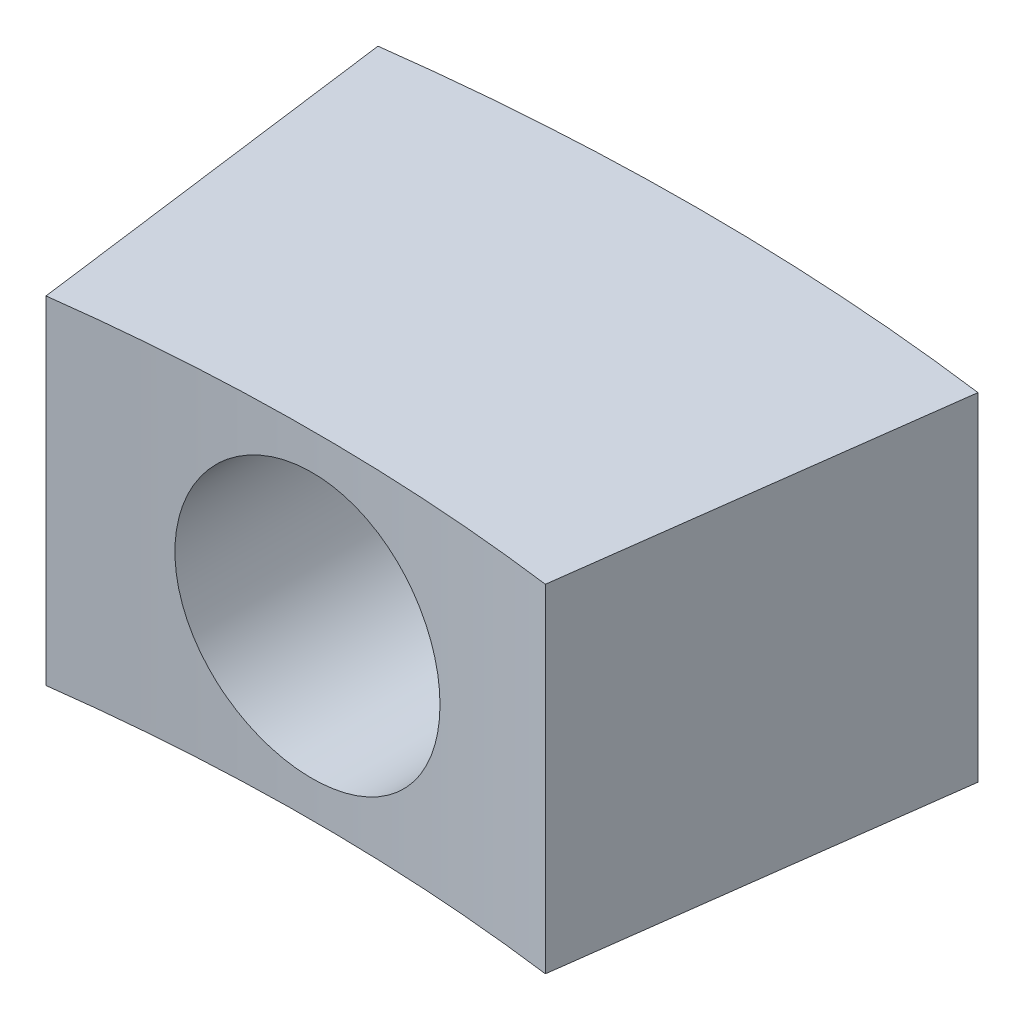
SolidWorks part; units mm, degrees
ref_plane "Front Plane" through (0, 0, 0) normal (0, 0, 1) x (1, 0, 0)
ref_plane "Top Plane" through (0, 0, 0) normal (0, 1, 0) x (1, 0, 0)
ref_plane "Right Plane" through (0, 0, 0) normal (1, 0, 0) x (0, 0, -1)
sketch "Sketch2" plane through (0, 0, 0) normal (0, 1, 0) x (1, 0, 0)
  line L0 (-6.2246, -0.408) -> (-5.1804, -8.3395)
  line L1 (5.1804, -8.3395) -> (6.2246, -0.408)
  line L2 (0, 16.9133) -> (0, -16.9133) construction
  line L3 (-2.75, -0.0794) -> (-2.75, -4.5125)
  line L4 (-2.75, -4.5125) -> (2.75, -4.5125)
  line L5 (2.75, -4.5125) -> (2.75, -0.0794)
  arc A0 (5.1804, -8.3395) -> (-5.1804, -8.3395) centre (0, -47.6885) ccw
  arc A1 (6.2246, -0.408) -> (-6.2246, -0.408) centre (0, -47.6885) ccw
  point P10 (0, 0)
  point P14 (0, -4.5125)
  point P15 (2.5267, -4.5125)
  dimension "D2" = 47.6885
  dimension "D3" = 15
  dimension "D4" = 5.5
  dimension "D5" = 0.0794
  dimension "D1" = 8
extrude "Boss-Extrude1" add sketch "Sketch2" along normal mid plane 7 contours L2 L4 L3 A1 L0 A0 | L2 A1 L3 L4 | L4 L2 A0 L1 A1 L5 | A1 L2 L4 L5 region at (-3.4143, 0, 4.643) region at (-1.3709, 0, 2.2694) region at (3.4143, 0, 4.643) region at (1.3709, 0, 2.2694)
sketch "Sketch3" plane through (0, 0, 0) normal (0, 0, 1) x (1, 0, 0)
  circle A0 centre (0, 0) radius 2.75
  dimension "D1" = 5.5
extrude "Cut-Extrude3" cut sketch "Sketch3" against normal through all and the other way through all contours A0 region at (0, 0, 0)
equation "\"Thiccness\"= 8mm"
equation "\"D1@Sketch2\"=\"Thiccness\""
equation "\"Coupler_ID\" = 3.755in"
equation "\"M4_Insert_OD\" = 5.5mm"
equation "\"Height\"= 7mm"
equation "\"D2@Sketch2\"=\"Coupler_ID\"/2"
equation "\"Angle\"= 15deg"
equation "\"D3@Sketch2\"=\"Angle\""
equation "\"D1@Boss-Extrude1\"=\"Height\""
equation "\"D4@Sketch2\"=\"M4_Insert_OD\""
equation "\"D1@Sketch3\"=\"M4_Insert_OD\""
